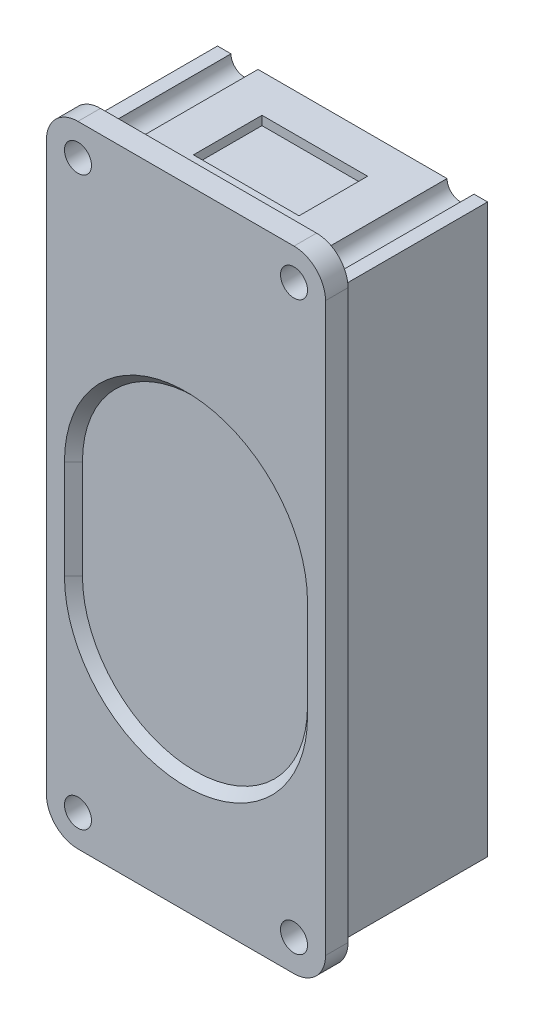
SolidWorks part; units mm, degrees
ref_plane "Front Plane" through (0, 0, 0) normal (0, 0, 1) x (1, 0, 0)
ref_plane "Top Plane" through (0, 0, 0) normal (0, 1, 0) x (1, 0, 0)
ref_plane "Right Plane" through (0, 0, 0) normal (1, 0, 0) x (0, 0, -1)
sketch "Sketch1" plane through (0, 0, 0) normal (0, 0, 1) x (1, 0, 0)
  line L1 (-12, 35) -> (12, 35)
  line L2 (-15.5, 31.5) -> (-15.5, -31.5)
  line L3 (-12, -35) -> (12, -35)
  line L4 (15.5, 31.5) -> (15.5, -31.5)
  line L5 (-15.5, 35) -> (15.5, -35) construction
  line L6 (-15.5, -35) -> (15.5, 35) construction
  arc A0 (12, -35) -> (15.5, -31.5) centre (12, -31.5) ccw
  arc A1 (-15.5, -31.5) -> (-12, -35) centre (-12, -31.5) ccw
  arc A2 (-12, 35) -> (-15.5, 31.5) centre (-12, 31.5) ccw
  arc A3 (12, 35) -> (15.5, 31.5) centre (12, 31.5) cw
  point P0 (0, 0)
  point P6 (0, 0)
  point P7 (0, 0)
  point P8 (0, 0)
  dimension "D3" = 3.5
  dimension "D1" = 31
  dimension "D2" = 70
extrude "Boss-Extrude1" add sketch "Sketch1" along normal blind 2.5
sketch "Sketch3" plane through (0, 0, 0) normal (1, 0, 0) x (0, 0, -1)
  line L0 (0, -35) -> (0, -31.5) construction
  line L1 (0, -31.5) -> (16, -31.5)
  line L2 (0, -31.5) -> (0, 31.5)
  line L3 (0, 31.5) -> (16, 31.5)
  line L4 (16, -31.5) -> (16, 31.5)
  line L5 (0, -31.5) -> (16, 31.5) construction
  line L6 (0, 31.5) -> (16, -31.5) construction
  point P0 (8, 0)
  point P7 (8, -6.4804)
  dimension "D1" = 16
  dimension "D2" = 63
extrude "Boss-Extrude2" add sketch "Sketch3" along normal mid plane 30
sketch "Sketch2" plane through (0, 0, 0) normal (0, 0, 1) x (1, 0, 0)
  line L0 (0, 0) -> (0, -29.7647) construction
  line L2 (-12, -35) -> (12, -35) construction
  line L3 (0, 0) -> (12.7, 0) construction
  circle A0 centre (-12, -31.5) radius 1.5
  circle A1 centre (12, -31.5) radius 1.5
  circle A2 centre (12, 31.5) radius 1.5
  circle A3 centre (-12, 31.5) radius 1.5
  dimension "D1" = 24
  dimension "D2" = 3.5
  dimension "D3" = 3
extrude "Cut-Extrude1" cut sketch "Sketch2" against normal through all both and the other way through all
ref_plane "Plane1" through (0, 0, 2.5) normal (0, 0, -1) x (-1, 0, 0)
sketch "Sketch4" plane through (0, 0, 2.5) normal (0, 0, 1) x (1, 0, 0)
  line L0 (0, 1.5) -> (0, -9.5) construction
  line L1 (13.5, 1.5) -> (13.5, -9.5)
  line L2 (-13.5, 1.5) -> (-13.5, -9.5)
  line L3 (-12, -35) -> (12, -35) construction
  arc A0 (13.5, 1.5) -> (-13.5, 1.5) centre (0, 1.5) ccw
  arc A1 (-13.5, -9.5) -> (13.5, -9.5) centre (0, -9.5) ccw
  point P2 (0, -4)
  point P7 (0, 0)
  point P8 (0, -23)
  point P9 (0, 15)
  point P12 (6.0735, 0)
  point P13 (0, -7)
  dimension "D1" = 38
  dimension "D2" = 27
  dimension "D3" = 12
extrude "Cut-Extrude2" cut sketch "Sketch4" against normal blind 1 draft 45
sketch "Sketch5" plane through (0, 31.5, 0) normal (0, 1, 0) x (1, 0, 0)
  line L0 (0, 0) -> (0, 16) construction
  line L1 (10.5, 16) -> (-10.5, 16) construction
  line L3 (-5.8663, 11.808) -> (5.8663, 11.808)
  line L4 (-5.8663, 11.808) -> (-5.8663, 4.192)
  line L5 (-5.8663, 4.192) -> (5.8663, 4.192)
  line L6 (5.8663, 11.808) -> (5.8663, 4.192)
  line L7 (-5.8663, 11.808) -> (5.8663, 4.192) construction
  line L8 (-5.8663, 4.192) -> (5.8663, 11.808) construction
  point P5 (0, 8)
extrude "Cut-Extrude3" cut sketch "Sketch5" against normal blind 1
